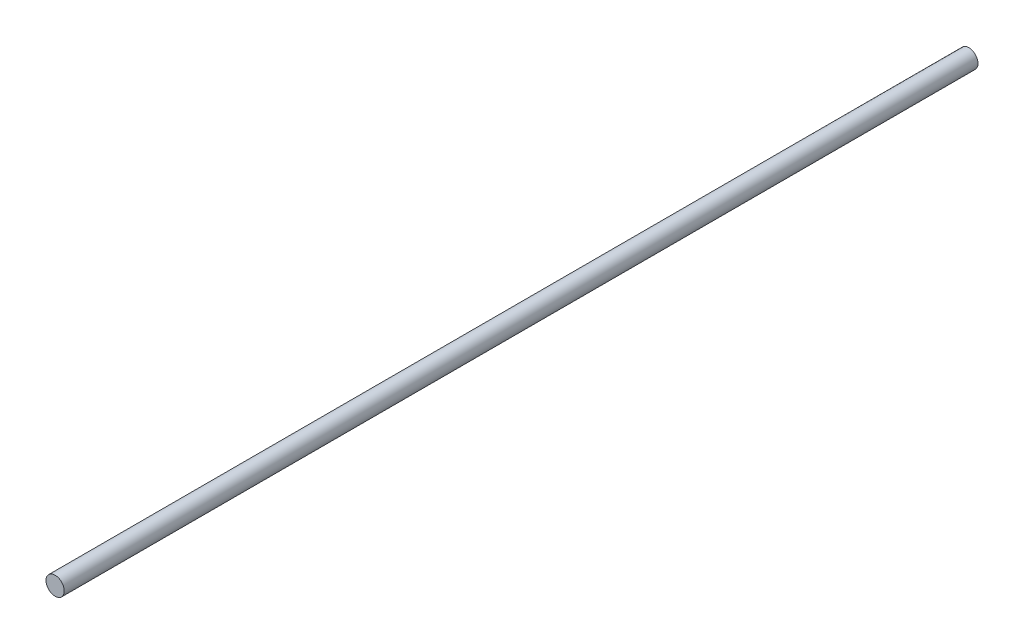
SolidWorks part; units mm, degrees
ref_plane "정면" through (0, 0, 0) normal (0, 0, 1) x (1, 0, 0)
ref_plane "윗면" through (0, 0, 0) normal (0, 1, 0) x (1, 0, 0)
ref_plane "우측면" through (0, 0, 0) normal (1, 0, 0) x (0, 0, -1)
sketch "스케치1" plane through (0, 0, 0) normal (0, 0, 1) x (1, 0, 0)
  circle A0 centre (0, 0) radius 2.5
  dimension "D1" = 5
extrude "보스-돌출1" add sketch "스케치1" along normal blind 250
